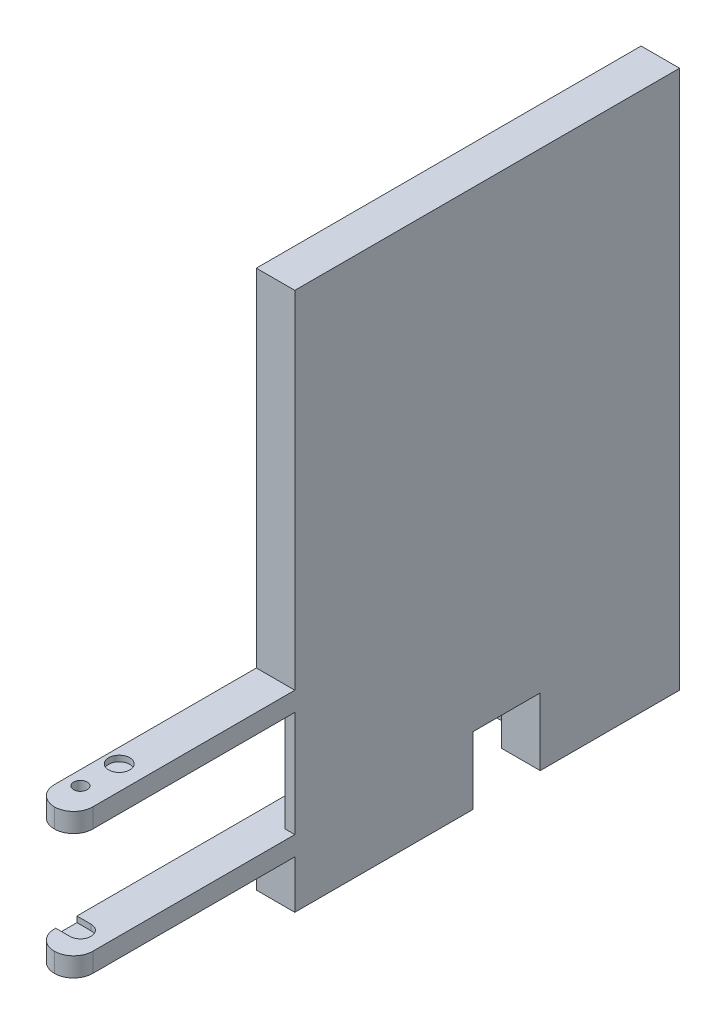
SolidWorks part; units mm, degrees
ref_plane "前视基准面" through (0, 0, 0) normal (0, 0, 1) x (1, 0, 0)
ref_plane "上视基准面" through (0, 0, 0) normal (0, 1, 0) x (1, 0, 0)
ref_plane "右视基准面" through (0, 0, 0) normal (1, 0, 0) x (0, 0, -1)
other "Configuration Table"
sketch "草图1" plane through (0, 0, 0) normal (0, 0, 1) x (1, 0, 0)
  line L9 (-10, -140) -> (10, -140)
  line L10 (-10, -140) -> (-10, 140)
  line L11 (-10, 140) -> (10, 140)
  line L12 (10, -140) -> (10, 140)
  line L13 (-10, -140) -> (10, 140) construction
  line L14 (-10, 140) -> (10, -140) construction
  point P0 (0, 0)
  dimension "D1" = 280
  dimension "D2" = 20
extrude "凸台-拉伸1" add sketch "草图1" along normal blind 200
sketch "草图2" plane through (-10, 0, 0) normal (-1, 0, 0) x (0, 0, 1)
  line L0 (200, -140) -> (0, -140) construction
  line L1 (72.4379, -140) -> (107.4379, -140)
  line L2 (72.4379, -140) -> (72.4379, -105)
  line L3 (72.4379, -105) -> (107.4379, -105)
  line L4 (107.4379, -140) -> (107.4379, -105)
  dimension "D1" = 35
  dimension "D2" = 35
  dimension "D3" = 72.4379
extrude "切除-拉伸1" cut sketch "草图2" against normal through all
sketch "草图4" plane through (0, -140, 0) normal (0, -1, 0) x (1, 0, 0)
  line L0 (-10, 72.4379) -> (-10, 0) construction
  line L1 (-10, 59.9879) -> (-45, 59.9879)
  line L2 (-10, 59.9879) -> (-10, 49.9879)
  line L3 (-10, 49.9879) -> (-45, 49.9879)
  line L4 (-45, 59.9879) -> (-45, 49.9879)
  line L5 (-10, 200) -> (-10, 107.4379) construction
  line L6 (-10, 134.9879) -> (-45, 134.9879)
  line L7 (-10, 134.9879) -> (-10, 144.9879)
  line L8 (-10, 144.9879) -> (-45, 144.9879)
  line L9 (-45, 134.9879) -> (-45, 144.9879)
  line L10 (-10, 200) -> (-10, 0) construction
  line L11 (10, 72.4379) -> (-10, 72.4379) construction
  point P14 (0, 0)
  point P15 (-45, 59.6949)
  point P16 (0, 0)
  dimension "D1" = 35
  dimension "D2" = 10
  dimension "D3" = 35
  dimension "D4" = 10
  dimension "D5" = 75
  dimension "D6" = 12.45
extrude "凸台-拉伸2" add sketch "草图4" against normal blind 150
sketch "草图5" plane through (0, 0, 144.9879) normal (0, 0, 1) x (1, 0, 0)
  line L0 (-45, 10) -> (-45, -140) construction
  line L1 (-45, -50) -> (-10, -50)
  line L2 (-45, -50) -> (-45, -105)
  line L3 (-45, -105) -> (-10, -105)
  line L4 (-10, -50) -> (-10, -105)
  line L5 (-10, 140) -> (-10, -140) construction
  line L6 (-10, -140) -> (-45, -140) construction
  dimension "D1" = 35
  dimension "D2" = 55
  dimension "D3" = 35
extrude "切除-拉伸3" cut sketch "草图5" against normal blind 24
sketch "草图6" plane through (0, 0, 200) normal (0, 0, 1) x (1, 0, 0)
  line L0 (-10, 140) -> (-10, -140) construction
  line L1 (-10, -50) -> (5, -50)
  line L2 (-10, -50) -> (-10, -105)
  line L3 (-10, -105) -> (5, -105)
  line L4 (5, -50) -> (5, -105)
  line L5 (-10, -50) -> (-45, -50) construction
  dimension "D1" = 55
  dimension "D2" = 15
extrude "切除-拉伸4" cut sketch "草图6" against normal up to surface (140.0121 mm away) up to face at (-27.5, -65, 59.9879)
sketch "草图7" plane through (0, -105, 0) normal (0, 1, 0) x (1, 0, 0)
  line L0 (-10, -66.2129) -> (10, -66.2129) construction
  line L1 (-10, -72.4379) -> (-10, -59.9879) construction
  line L2 (10, -72.4379) -> (10, 0) construction
  line L3 (-2.6613, -71.7129) -> (-10, -71.7129)
  line L4 (-10, -71.7129) -> (-10, -60.7129)
  line L5 (-10, -60.7129) -> (-2.6613, -60.7129)
  arc A0 (-2.6613, -71.7129) -> (-2.6613, -60.7129) centre (-2.6613, -66.2129) ccw
  dimension "D1" = 11
extrude "切除-拉伸5" cut sketch "草图7" along normal blind 58 and the other way blind 3
sketch "草图9" plane through (0, 0, 200) normal (0, 0, 1) x (1, 0, 0)
  line L0 (10, -140) -> (10, 140) construction
  line L1 (-10, -105) -> (10, -105)
  line L2 (-10, -105) -> (-10, -115)
  line L3 (-10, -115) -> (10, -115)
  line L4 (10, -105) -> (10, -115)
  line L6 (-10, -50) -> (10, -50)
  line L7 (-10, -50) -> (-10, -40)
  line L8 (-10, -40) -> (10, -40)
  line L9 (10, -50) -> (10, -40)
  dimension "D1" = 10
  dimension "D2" = 10
  dimension "D3" = 55
extrude "凸台-拉伸3" add sketch "草图9" along normal blind 115
ref_plane "基准面1" through (0, 0, 182.4939) normal (0, 0, -1) x (-1, 0, 0)
mirror "镜向1" about plane through (0, 0, 182.4939) normal (0, 0, -1) of "切除-拉伸5"
sketch "草图10" plane through (0, -40, 0) normal (0, 1, 0) x (1, 0, 0)
  circle A2 centre (-2.6613, -298.775) radius 3.5
  dimension "D1" = 7
extrude "切除-拉伸7" cut sketch "草图10" against normal blind 20
sketch "草图11" plane through (0, -40, 0) normal (0, 1, 0) x (1, 0, 0)
  line L0 (10, -315) -> (-10, -315) construction
  line L1 (-10, -315) -> (-10, -200) construction
  circle A0 centre (-2.5, -278.775) radius 5.5
  dimension "D1" = 11
  dimension "D2" = 36.225
  dimension "D3" = 7.5
extrude "切除-拉伸8" cut sketch "草图11" against normal blind 3
fillet "圆角1" radius 10 4 edges at (10, -45, 315) (10, -110, 315) (-10, -45, 315) (-10, -110, 315)
